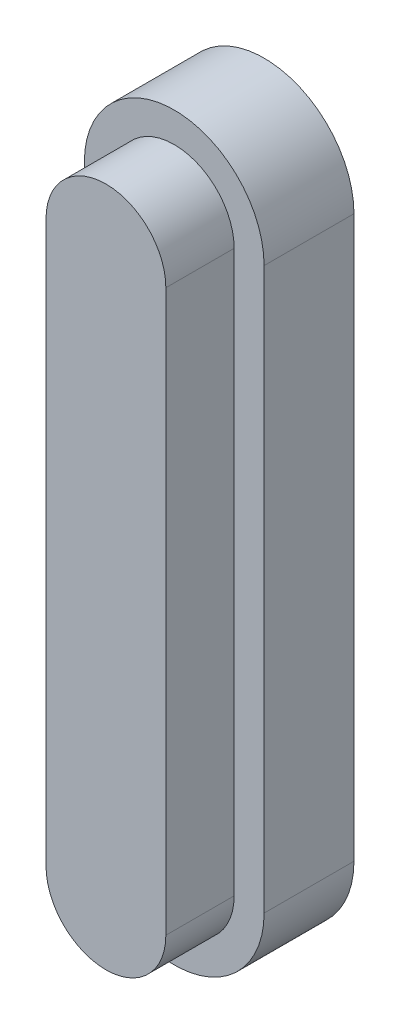
SolidWorks part; units mm, degrees
ref_plane "Front Plane" through (0, 0, 0) normal (0, 0, 1) x (1, 0, 0)
ref_plane "Top Plane" through (0, 0, 0) normal (0, 1, 0) x (1, 0, 0)
ref_plane "Right Plane" through (0, 0, 0) normal (1, 0, 0) x (0, 0, -1)
sketch "Sketch1" plane through (0, 0, 0) normal (0, 0, 1) x (1, 0, 0)
  line L0 (1.5875, -14.859) -> (1.5875, 0)
  line L1 (-1.5875, 0) -> (-1.5875, -14.859)
  line L2 (2.3812, -14.859) -> (2.3812, 0)
  line L3 (-2.3812, 0) -> (-2.3812, -14.859)
  arc A0 (-1.5875, -14.859) -> (1.5875, -14.859) centre (0, -14.859) ccw
  arc A1 (1.5875, 0) -> (-1.5875, 0) centre (0, 0) ccw
  arc A2 (2.3812, 0) -> (-2.3812, 0) centre (0, 0) ccw
  arc A3 (-2.3812, -14.859) -> (2.3812, -14.859) centre (0, -14.859) ccw
  point P6 (0, 0)
  point P8 (0, 0)
  point P15 (0, 0)
  point P16 (0, 0)
  dimension "D1" = 1.5875
  dimension "D2" = 14.859
  dimension "D3" = 0.7937
extrude "Boss-Extrude1" add sketch "Sketch1" along normal blind 2.3813
extrude "Boss-Extrude2" add sketch "Sketch1<5>" along normal blind 4.191 contours L0 A1 L1 A0 region at (0, -7.4295, 0)
sketch "Sketch1<5>" plane through (0, 0, 0) normal (0, 0, 1) x (1, 0, 0) same geometry as "Sketch1"
